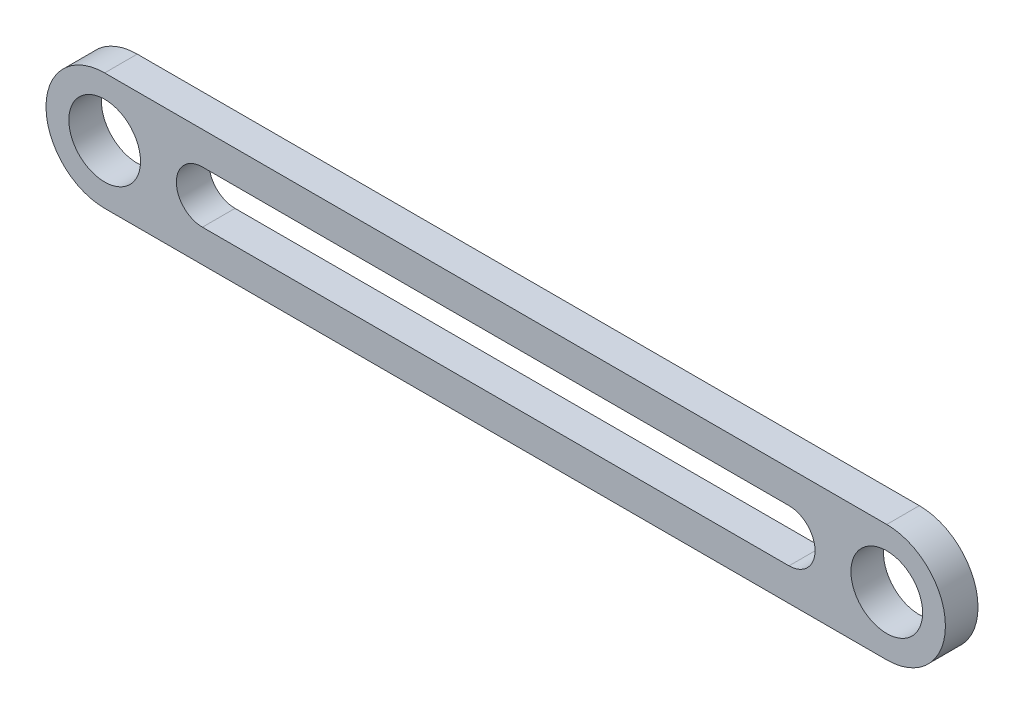
SolidWorks part; units mm, degrees
material "Thornel Mat VMA"
ref_plane "Front Plane" through (0, 0, 0) normal (0, 0, 1) x (1, 0, 0)
ref_plane "Top Plane" through (0, 0, 0) normal (0, 1, 0) x (1, 0, 0)
ref_plane "Right Plane" through (0, 0, 0) normal (1, 0, 0) x (0, 0, -1)
sketch "Sketch1" plane through (0, 0, 0) normal (0, 0, 1) x (1, 0, 0)
  line L0 (-60, 0) -> (60, 0) construction
  line L1 (-60, 9) -> (60, 9)
  line L2 (-60, -9) -> (60, -9)
  arc A0 (-60, 9) -> (-60, -9) centre (-60, 0) ccw
  arc A1 (60, -9) -> (60, 9) centre (60, 0) ccw
  circle A2 centre (-60, 0) radius 5.5
  circle A3 centre (60, 0) radius 5.5
  point P3 (0, 0)
  dimension "D2" = 11
  dimension "D3" = 9
  dimension "D1" = 120
extrude "Boss-Extrude1" add sketch "Sketch1" along normal blind 5
sketch "Sketch2" plane through (0, 0, 5) normal (0, 0, 1) x (1, 0, 0)
  line L0 (-45, 0) -> (45, 0) construction
  line L1 (-45, 4) -> (45, 4)
  line L2 (-45, -4) -> (45, -4)
  arc A0 (-45, 4) -> (-45, -4) centre (-45, 0) ccw
  arc A1 (45, -4) -> (45, 4) centre (45, 0) ccw
  point P3 (0, 0)
  point P8 (0, 0)
  dimension "D1" = 4
  dimension "D2" = 90
extrude "Cut-Extrude1" cut sketch "Sketch2" against normal blind 10
